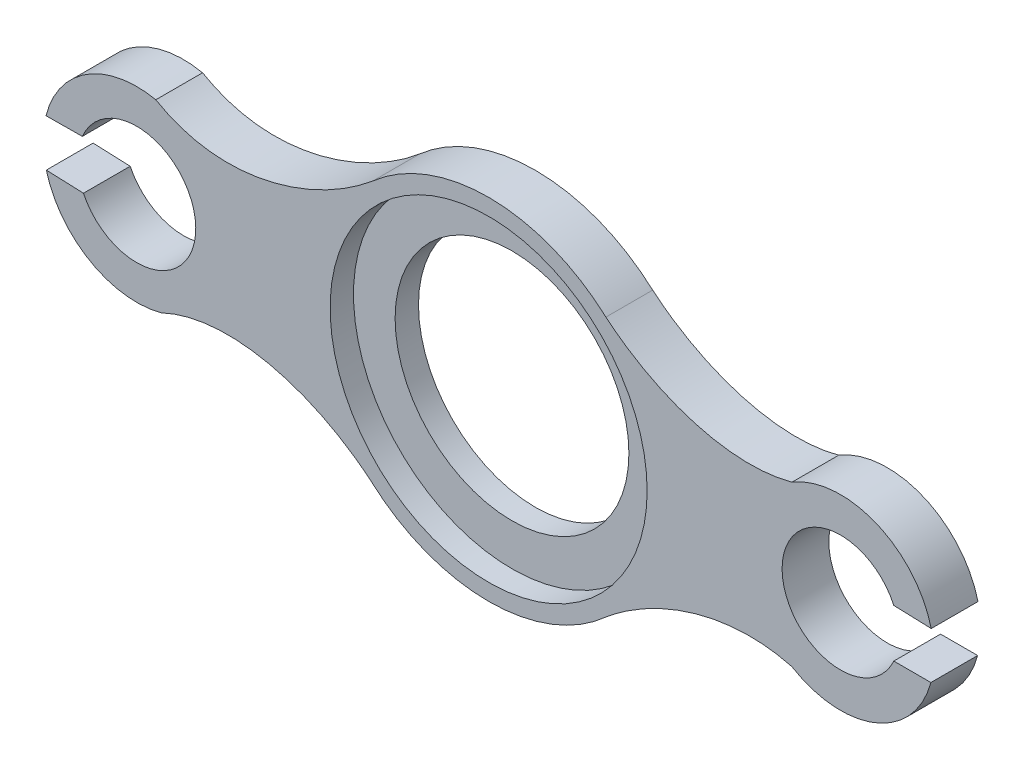
SolidWorks part; units mm, degrees
material "AISI 1020"
ref_plane "Front Plane" through (0, 0, 0) normal (0, 0, 1) x (1, 0, 0)
ref_plane "Top Plane" through (0, 0, 0) normal (0, 1, 0) x (1, 0, 0)
ref_plane "Right Plane" through (0, 0, 0) normal (1, 0, 0) x (0, 0, -1)
other "Center of Mass"
sketch "Sketch1" plane through (0, 0, 0) normal (0, 0, 1) x (1, 0, 0)
  line L0 (-189.3198, 10.3878) -> (-173.7882, 10.509)
  line L1 (-189.1764, -9.6656) -> (-173.3042, -10.3037)
  line L2 (173.3042, 10.3037) -> (189.3198, 9.7498)
  line L3 (173.3042, -10.3037) -> (189.1764, -10.3037)
  circle A0 centre (0, 0) radius 67.8
  circle A1 centre (0, 0) radius 50
  circle A2 centre (0, 0) radius 74.853
  arc A3 (-173.7882, 10.509) -> (-173.3042, -10.3037) centre (-150.5262, 0.638) cw
  arc A4 (-189.3198, 10.3878) -> (-189.1764, -9.6656) centre (-150.5262, 0.638) cw
  arc A5 (173.3042, 10.3037) -> (173.3042, -10.3037) centre (150.5262, 0) ccw
  arc A6 (189.3198, 9.7498) -> (189.1764, -10.3037) centre (150.5262, 0) ccw
  spline S0 degree 3 poles (-142.3484, 39.7931) (-112.1812, 22.0907) (-72.1888, 36.2337) (-47.9761, 57.4566) knots 0 0 0 0 1 1 1 1
  spline S1 degree 3 poles (142.4761, 39.1816) (111.8282, 22.9867) (72.3927, 35.5922) (47.9761, 57.4566) knots 0 0 0 0 1 1 1 1
  spline S2 degree 3 poles (-142.4761, -39.1816) (-111.8282, -22.9867) (-72.3927, -35.5922) (-47.9761, -57.4566) knots 0 0 0 0 1 1 1 1
  spline S3 degree 3 poles (142.4761, -39.1816) (111.8282, -22.9867) (72.3927, -35.5922) (47.9761, -57.4566) knots 0 0 0 0 1 1 1 1
  dimension "D2" = 100
extrude "Boss-Extrude11" add sketch "Sketch1" along normal blind 20 contours A4 S2 S0 L0 A3 L1 | A4 S2 A2 S0 | S3 A6 S1 A2 | A2 | A6 L3 A5 L2 | A0 region at (-171.1554, 33.5906, 0) region at (-91.3299, -0.1434, 0) region at (91.3466, 0, 0)
extrude "Boss-Extrude12" add sketch "Sketch1<14>" along normal blind 10 contours A0 A1 region at (-65.8823, 0, 0)
sketch "Sketch1<14>" plane through (0, 0, 0) normal (0, 0, 1) x (1, 0, 0) same geometry as "Sketch1"
